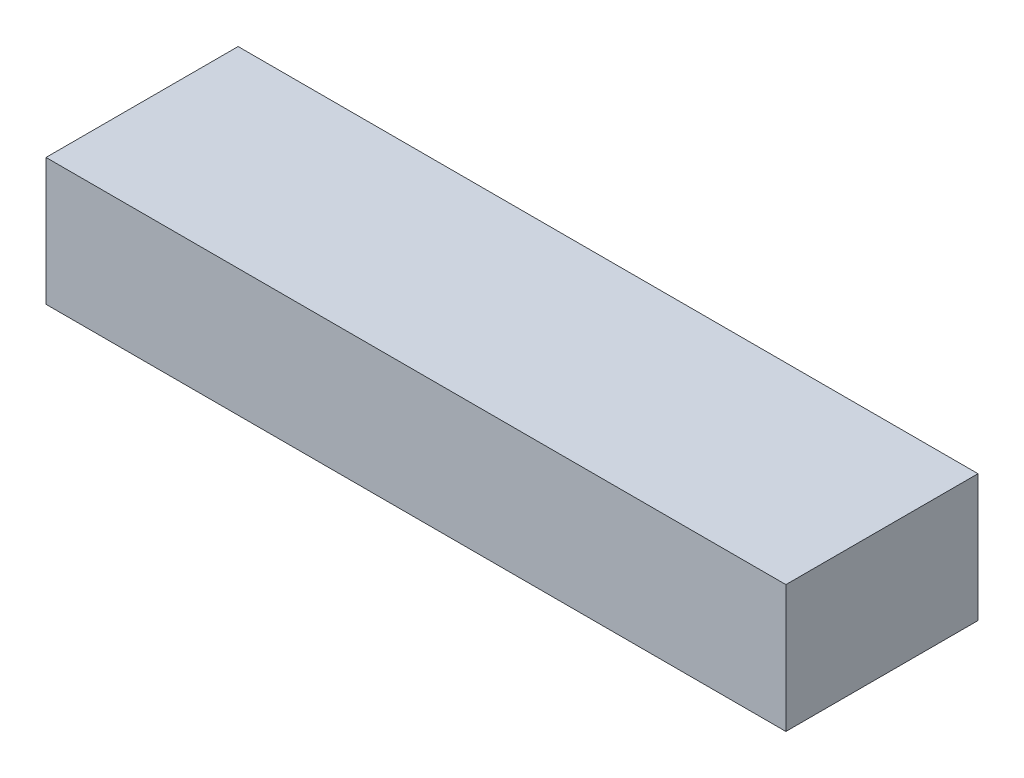
SolidWorks part; units mm, degrees
ref_plane "Front Plane" through (0, 0, 0) normal (0, 0, 1) x (1, 0, 0)
ref_plane "Top Plane" through (0, 0, 0) normal (0, 1, 0) x (1, 0, 0)
ref_plane "Right Plane" through (0, 0, 0) normal (1, 0, 0) x (0, 0, -1)
sketch "Sketch1" plane through (0, 0, 0) normal (0, 1, 0) x (1, 0, 0)
  line L1 (570, -148) -> (-570, -148)
  line L2 (570, -148) -> (570, 148)
  line L3 (570, 148) -> (-570, 148)
  line L4 (-570, -148) -> (-570, 148)
  line L5 (570, -148) -> (-570, 148) construction
  line L6 (570, 148) -> (-570, -148) construction
  point P0 (0, 0)
  dimension "D1" = 1140
  dimension "D2" = 296
extrude "Boss-Extrude1" add sketch "Sketch1" along normal blind 196
equation "\"assembly\"= 0"
equation "\"thickness 1\"= 2"
equation "\"thickness 2\"= 3"
equation "\"connecting flange\"= 35"
equation "\"main\"= 0"
equation "\"main length\"= 1200"
equation "\"main width\"= 1200"
equation "\"divider panel distance offset\"= 296"
equation "\"side panel\"= 0"
equation "\"access hatch length\"= 600"
equation "\"access hatch width\"= 450"
equation "\"access hatch offset X\"= 100"
equation "\"access hatch offset Y\"= 100"
equation "\"side panel length\"= 1200"
equation "\"side panel width\"= 950"
equation "\"back panel\"= 0"
equation "\"back panel access hatch length\"= 1150"
equation "\"back panel access hatch width\"= 206"
equation "\"back panel access hatch flange\"= 40"
equation "\"drift eliminator\"= 0"
equation "\"drift eliminator size offset\"= 10"
equation "\"sump\"= 0"
equation "\"D1@Boss-Extrude1\"=\"drift eliminator width\""
equation "\"D1@Sketch1\"=\"drift eliminator length\""
equation "\"D2@Sketch1\"=\"drift eliminator depth\""
